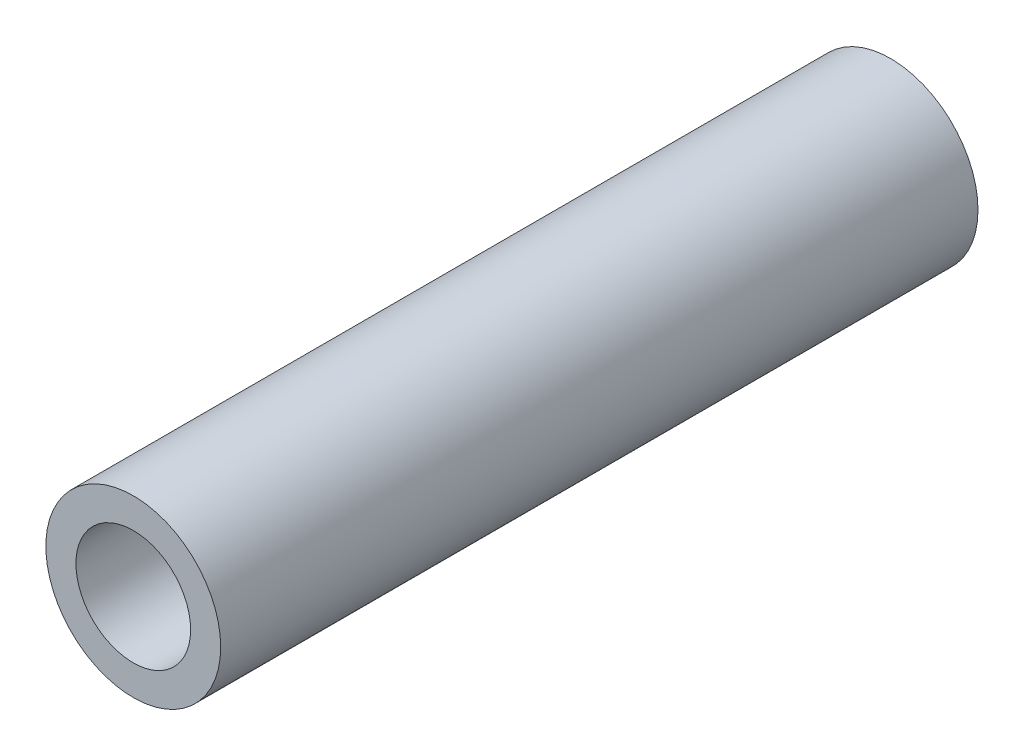
SolidWorks part; units mm, degrees
ref_plane "Front" through (0, 0, 0) normal (0, 0, 1) x (1, 0, 0)
ref_plane "Top" through (0, 0, 0) normal (0, 1, 0) x (1, 0, 0)
ref_plane "Right" through (0, 0, 0) normal (1, 0, 0) x (0, 0, -1)
sketch "Sketch1" plane through (0, 0, 0) normal (0, 0, 1) x (1, 0, 0)
  circle A0 centre (0, 0) radius 6.35
  circle A1 centre (0, 0) radius 4.165
  dimension "D1" = 12.7
  dimension "D2" = 8.33
extrude "Boss-Extrude1" add sketch "Sketch1" along normal blind 55
